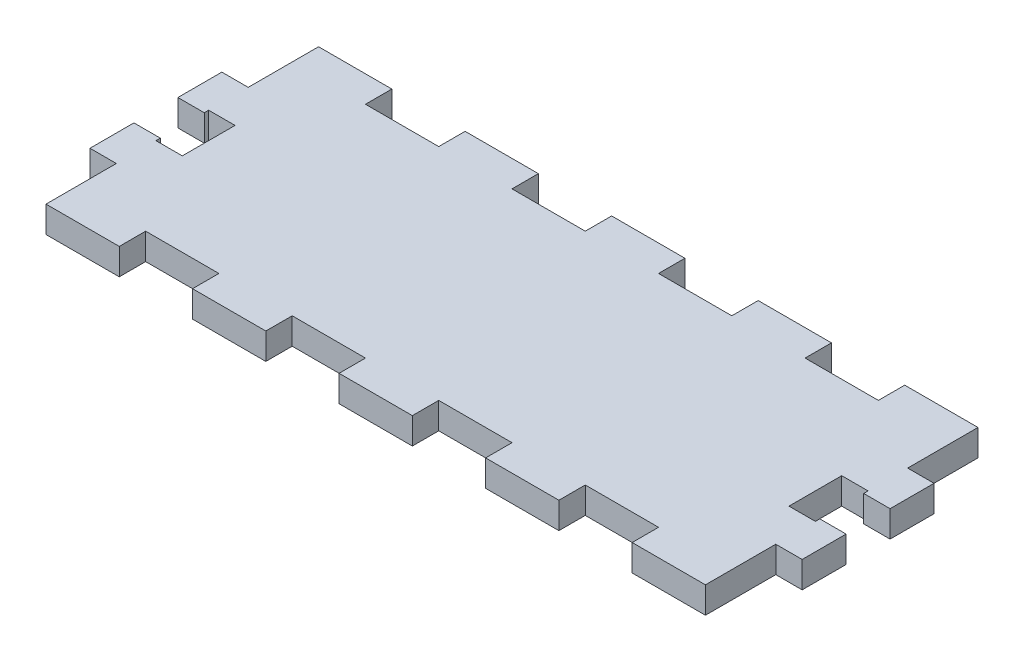
SolidWorks part; units mm, degrees
ref_plane "Front Plane" through (0, 0, 0) normal (0, 0, 1) x (1, 0, 0)
ref_plane "Top Plane" through (0, 0, 0) normal (0, 1, 0) x (1, 0, 0)
ref_plane "Right Plane" through (0, 0, 0) normal (1, 0, 0) x (0, 0, -1)
sketch "Sketch1" plane through (0, 0, 0) normal (0, 1, 0) x (1, 0, 0)
  line L1 (-81, 31) -> (81, 31)
  line L2 (-81, 31) -> (-81, -31)
  line L3 (-81, -31) -> (81, -31)
  line L4 (81, 31) -> (81, -31)
  line L5 (-81, 31) -> (81, -31) construction
  line L6 (-81, -31) -> (81, 31) construction
  point P0 (0, 0)
  dimension "D1" = 162
  dimension "D2" = 62
sketch "Sketch2" plane through (0, 0, 0) normal (0, 0, 1) x (1, 0, 0)
  line L0 (0, 0) -> (0, 6) construction
  line L1 (-81, 0) -> (81, 0) construction
extrude "Boss-Extrude1" add sketch "Sketch1" along normal up to vertex (6 mm away) contours L2 L3 L4 L1 up to point (0, 6, 0)
sketch "Sketch3" plane through (0, 0, 0) normal (0, -1, 0) x (-1, 0, 0)
  line L0 (81, 31) -> (81, -31) construction
  line L1 (75, 15) -> (81, 15)
  line L2 (75, 15) -> (75, 31)
  line L3 (75, 31) -> (81, 31)
  line L4 (81, 15) -> (81, 31)
  line L5 (75, -15) -> (81, -15)
  line L6 (75, -15) -> (75, -31)
  line L7 (75, -31) -> (81, -31)
  line L8 (81, -15) -> (81, -31)
  line L9 (81, -5) -> (75, -5)
  line L10 (81, -5) -> (81, 5)
  line L11 (81, 5) -> (75, 5)
  line L12 (75, -5) -> (75, 5)
  line L13 (81, -5) -> (75, -5) construction
  line L14 (75, -6) -> (75, 6) construction
  line L15 (69, 6) -> (75, 6)
  line L16 (69, 6) -> (69, -6)
  line L17 (69, -6) -> (75, -6)
  line L18 (75, 6) -> (75, -6)
  line L19 (75, -6) -> (69, -6) construction
  line M1 (81, 31) -> (-81, 31)
  line M3 (-81, -31) -> (81, -31)
  line M4 (81, -31) -> (81, 31)
extrude "Cut-Extrude1" cut sketch "Sketch3" against normal through all contours L5 L6 M3 M4 | L12 L9 L11 M4 | L18 L15 L16 L17 L12 | L2 L1 M4 M1 region at (-78, 0, -23) region at (-78, 0, 23) region at (-78, 0, 0) region at (-72, 0, 0)
sketch "Sketch4" plane through (0, 0, 0) normal (0, -1, 0) x (1, 0, 0)
  line L0 (-75, -31) -> (81, -31) construction
  line L1 (-58.3333, -25) -> (-41.6667, -25)
  line L2 (-58.3333, -25) -> (-58.3333, -31)
  line L3 (-58.3333, -31) -> (-41.6667, -31)
  line L4 (-41.6667, -25) -> (-41.6667, -31)
  line L5 (-8.3333, -25) -> (-8.3333, -31) construction
  line L6 (-25, -25) -> (-8.3333, -25)
  line L7 (-25, -25) -> (-25, -31)
  line L8 (-25, -31) -> (-8.3333, -31)
  line L9 (-8.3333, -25) -> (-8.3333, -31)
  line L10 (-41.6667, -25) -> (-41.6667, -31) construction
extrude "Cut-Extrude2" cut sketch "Sketch4" against normal through all
mirror "Mirror1" about plane through (0, 0, 0) normal (0, 0, 1) of "Cut-Extrude2"
mirror "Mirror2" about plane through (0, 0, 0) normal (1, 0, 0) of "Cut-Extrude1", "Mirror1"
equation "\"glass_width\"= 150"
equation "\"glass_height\"= 100"
equation "\"glass_thickness\"= 4"
equation "\"brood_space\"= 42"
equation "\"t1\"= 6"
equation "\"t2\"= 6"
equation "\"box_depth\"= \"brood_space\" + \"glass_thickness\" + \"glass_thickness\" + \"t2\" + \"t2\""
equation "\"box_width\"= \"glass_width\" + \"t1\" + \"t1\""
equation "\"food_height\"= 70"
equation "\"box_height\"= \"glass_height\" + ( \"t1\" * 3 ) + \"food_height\""
equation "\"D1@Sketch1\"=\"box_width\""
equation "\"D1@Sketch2\"=\"t1\""
equation "\"D2@Sketch1\"=\"box_depth\""
equation "\"entry_height\"= 24"
equation "\"entry_diameter\"= 8"
equation "\"food_top_clearance\"= 10"
equation "\"bar_width\"= 20"
equation "\"glassblocker_lower_height\"= 10"
equation "\"lower_edge_stickout\"=6"
